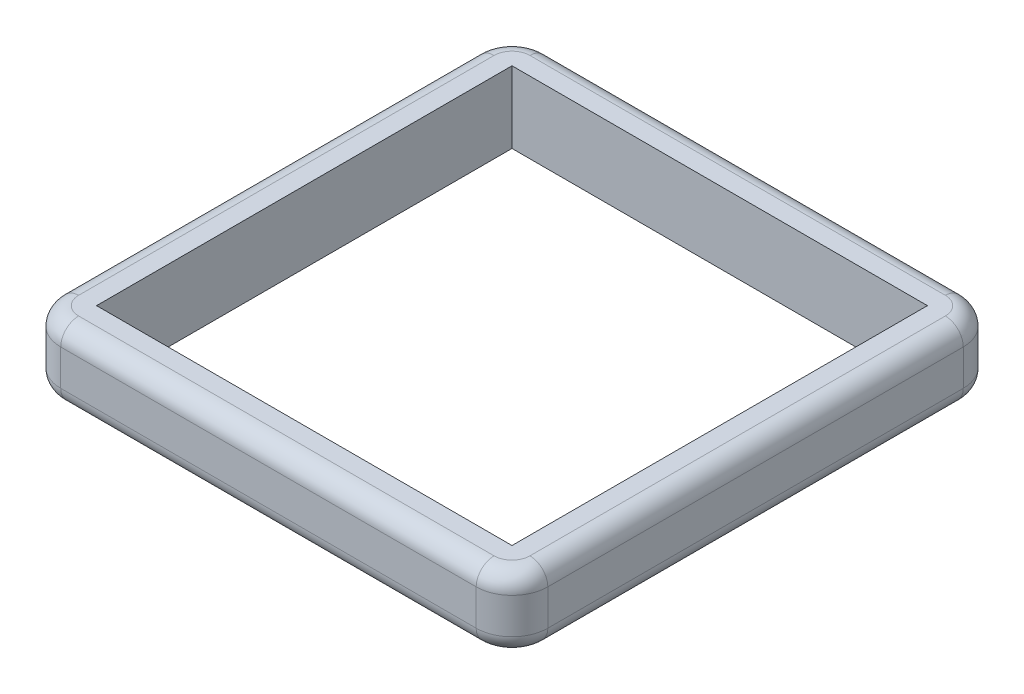
SolidWorks part; units mm, degrees
material "Polyurethane Foam Flexible"
ref_plane "Front Plane" through (0, 0, 0) normal (0, 0, 1) x (1, 0, 0)
ref_plane "Top Plane" through (0, 0, 0) normal (0, 1, 0) x (1, 0, 0)
ref_plane "Right Plane" through (0, 0, 0) normal (1, 0, 0) x (0, 0, -1)
sketch "Sketch1" plane through (0, 0, 0) normal (1, 0, 0) x (0, 0, -1)
  line L0 (-31.75, 0) -> (-31.75, -63.5)
  line L1 (31.75, 0) -> (31.75, -95.25)
  line L2 (0, -95.25) -> (31.75, -95.25)
  line L3 (31.75, 0) -> (31.75, 31.75)
  line L4 (0, 31.75) -> (31.75, 31.75)
  arc A0 (0, 31.75) -> (-31.75, 0) centre (0, 0) ccw
  arc A1 (-31.75, -63.5) -> (0, -95.25) centre (0, -63.5) ccw
  arc A2 (31.75, 0) -> (0, 31.75) centre (0, 0) ccw construction
  arc A3 (0, -31.75) -> (31.75, 0) centre (0, 0) ccw construction
  arc A4 (31.75, -63.5) -> (0, -31.75) centre (0, -63.5) ccw construction
  arc A5 (-31.75, 0) -> (0, -31.75) centre (0, 0) ccw construction
  arc A6 (0, -31.75) -> (-31.75, -63.5) centre (0, -63.5) ccw construction
  arc A7 (0, -95.25) -> (31.75, -63.5) centre (0, -63.5) ccw construction
  dimension "D1" = 63.5
  dimension "D2" = 63.5
extrude "Boss-Extrude1" add sketch "Sketch1" along normal blind 736.6 contours L0 A1 L2 L1 L3 L4 A0 region at (0, -31.75, -1.3979)
sketch "Sketch8" plane through (736.6, 0, 0) normal (1, 0, 0) x (0, 0, -1)
  line L8 (-31.75, 0) -> (-31.75, -63.5)
  line L9 (0, -95.25) -> (31.75, -95.25)
  line L10 (31.75, -95.25) -> (31.75, 31.75)
  line L11 (31.75, 31.75) -> (0, 31.75)
  line L12 (-31.75, 0) -> (-31.75, -63.5)
  line L13 (0, -95.25) -> (31.75, -95.25)
  line L14 (31.75, -95.25) -> (31.75, 31.75)
  line L15 (31.75, 31.75) -> (0, 31.75)
  arc A4 (-31.75, -63.5) -> (0, -95.25) centre (0, -63.5) ccw
  arc A5 (0, 31.75) -> (-31.75, 0) centre (0, 0) ccw
  arc A6 (-31.75, -63.5) -> (0, -95.25) centre (0, -63.5) ccw
  arc A7 (0, 31.75) -> (-31.75, 0) centre (0, 0) ccw
  dimension "D1" = 0
revolve "Revolve13" add sketch "Sketch8" angle 90 about L14
sketch "Sketch15" plane through (0, 0, -31.75) normal (-1, 0, 0) x (0, 0, 1)
  line L14 (63.5, -63.5) -> (63.5, 0)
  line L20 (31.75, 31.75) -> (0, 31.75)
  line L21 (0, 31.75) -> (0, -95.25)
  line L22 (0, -95.25) -> (31.75, -95.25)
  line L23 (63.5, -63.5) -> (63.5, 0)
  line L24 (31.75, 31.75) -> (0, 31.75)
  line L25 (0, 31.75) -> (0, -95.25)
  line L26 (0, -95.25) -> (31.75, -95.25)
  arc A8 (63.5, 0) -> (31.75, 31.75) centre (31.75, 0) ccw
  arc A9 (31.75, -95.25) -> (63.5, -63.5) centre (31.75, -63.5) ccw
  arc A10 (63.5, 0) -> (31.75, 31.75) centre (31.75, 0) ccw
  arc A11 (31.75, -95.25) -> (63.5, -63.5) centre (31.75, -63.5) ccw
  dimension "D1" = 0
revolve "Revolve12" add sketch "Sketch15" angle 90 about L25 region at (0, -31.75, -1.3979)
sketch "Sketch7" plane through (0, 0, -31.75) normal (0, 0, -1) x (-1, 0, 0)
  line L6 (-800.1, 0) -> (-800.1, -63.5)
  line L7 (-768.35, -95.25) -> (-736.6, -95.25)
  line L8 (-736.6, -95.25) -> (-736.6, 31.75)
  line L9 (-736.6, 31.75) -> (-768.35, 31.75)
  line L10 (-800.1, 0) -> (-800.1, -63.5)
  line L11 (-768.35, -95.25) -> (-736.6, -95.25)
  line L12 (-736.6, -95.25) -> (-736.6, 31.75)
  line L13 (-736.6, 31.75) -> (-768.35, 31.75)
  arc A4 (-768.35, 31.75) -> (-800.1, 0) centre (-768.35, 0) ccw
  arc A5 (-800.1, -63.5) -> (-768.35, -95.25) centre (-768.35, -63.5) ccw
  arc A6 (-768.35, 31.75) -> (-800.1, 0) centre (-768.35, 0) ccw
  arc A7 (-800.1, -63.5) -> (-768.35, -95.25) centre (-768.35, -63.5) ccw
  line M4 (-736.6, 31.75) -> (-736.6, -95.25)
  dimension "D1" = 0
extrude "Boss-Extrude3" add sketch "Sketch7" along normal blind 736.6 contours M4 | M4 region at (766.9521, -31.75, -31.75)
sketch "Sketch12" plane through (1454.15, 0, -768.35) normal (0, 0, -1) x (-1, 0, 0)
  line L13 (654.05, 0) -> (654.05, -63.5)
  line L20 (685.8, -95.25) -> (717.55, -95.25)
  line L21 (717.55, -95.25) -> (717.55, 31.75)
  line L22 (717.55, 31.75) -> (685.8, 31.75)
  line L23 (654.05, 0) -> (654.05, -63.5)
  line L24 (685.8, -95.25) -> (717.55, -95.25)
  line L25 (717.55, -95.25) -> (717.55, 31.75)
  line L26 (717.55, 31.75) -> (685.8, 31.75)
  arc A8 (654.05, -63.5) -> (685.8, -95.25) centre (685.8, -63.5) ccw
  arc A9 (685.8, 31.75) -> (654.05, 0) centre (685.8, 0) ccw
  arc A10 (654.05, -63.5) -> (685.8, -95.25) centre (685.8, -63.5) ccw
  arc A11 (685.8, 31.75) -> (654.05, 0) centre (685.8, 0) ccw
  dimension "D1" = 0
revolve "Revolve2" add sketch "Sketch12" angle 90 about L25 region at (766.9521, -31.75, -768.35)
sketch "Sketch9" plane through (0, 0, -31.75) normal (0, 0, -1) x (-1, 0, 0)
  line L0 (31.75, 31.75) -> (0, 31.75)
  line L1 (31.75, -95.25) -> (0, -95.25)
  line L2 (0, 31.75) -> (0, -95.25)
  line L3 (63.5, 0) -> (63.5, -63.5)
  line L4 (-736.6, 31.75) -> (0, 31.75) construction
  line L5 (0, -95.25) -> (0, 31.75) construction
  circle A0 centre (31.75, 0) radius 31.75
  circle A1 centre (31.75, -63.5) radius 31.75
  line M5 (0, -95.25) -> (0, 31.75)
  dimension "D1" = 63.5
  dimension "D2" = 0
  dimension "D3" = 0
extrude "Boss-Extrude4" add sketch "Sketch9" along normal blind 736.6 contours A0 L0 L2 | A0 | A1 A0 L2 | A1 L3 A0 | A1 | A1 L1 M5 region at (-7.0919, 24.6581, -31.75) region at (-31.75, 0, -31.75) region at (-56.4081, -31.75, -31.75) region at (-7.0919, -31.75, -31.75) region at (-31.75, -63.5, -31.75) region at (-7.0919, -88.1581, -31.75)
sketch "Sketch14" plane through (0, 0, -768.35) normal (0, 0, -1) x (-1, 0, 0)
  line L12 (0, 31.75) -> (0, -95.25)
  line L13 (0, -95.25) -> (31.75, -95.25)
  line L14 (63.5, -63.5) -> (63.5, 0)
  line L15 (31.75, 31.75) -> (0, 31.75)
  line L16 (0, 31.75) -> (0, -95.25)
  line L17 (0, -95.25) -> (31.75, -95.25)
  line L18 (63.5, -63.5) -> (63.5, 0)
  line L19 (31.75, 31.75) -> (0, 31.75)
  arc A4 (31.75, -95.25) -> (63.5, -63.5) centre (31.75, -63.5) ccw
  arc A5 (63.5, 0) -> (31.75, 31.75) centre (31.75, 0) ccw
  arc A6 (31.75, -95.25) -> (63.5, -63.5) centre (31.75, -63.5) ccw
  arc A7 (63.5, 0) -> (31.75, 31.75) centre (31.75, 0) ccw
  dimension "D1" = 0
revolve "Revolve10" add sketch "Sketch14" angle 90 about L16 region at (-30.3521, -31.75, -768.35)
sketch "Sketch10" plane through (0, 0, 0) normal (1, 0, 0) x (0, 0, -1)
  line L4 (800.1, 31.75) -> (768.35, 31.75)
  line L7 (768.35, 31.75) -> (768.35, -95.25)
  line L8 (768.35, -95.25) -> (800.1, -95.25)
  line L9 (831.85, -63.5) -> (831.85, 0)
  line L10 (800.1, 31.75) -> (768.35, 31.75)
  line L12 (768.35, -95.25) -> (800.1, -95.25)
  line L13 (831.85, -63.5) -> (831.85, 0)
  line L15 (768.35, 31.75) -> (768.35, -95.25)
  arc A4 (800.1, -95.25) -> (831.85, -63.5) centre (800.1, -63.5) ccw
  arc A5 (831.85, 0) -> (800.1, 31.75) centre (800.1, 0) ccw
  arc A6 (800.1, -95.25) -> (831.85, -63.5) centre (800.1, -63.5) ccw
  arc A7 (831.85, 0) -> (800.1, 31.75) centre (800.1, 0) ccw
  line M7 (768.35, -95.25) -> (768.35, 31.75)
  dimension "D1" = 0
extrude "Boss-Extrude5" add sketch "Sketch10" along normal blind 736.6 separate body contours M7 | M7 region at (0, -31.75, -798.7021)
combine bodies "Combine1" operation type add bodies to combine 105 115 108
equation "\"foamlength\"=29"
equation "\"D1@Boss-Extrude1\"=\"foamlength\""
equation "\"D1@Boss-Extrude3\"=\"foamlength\""
equation "\"D1@Boss-Extrude4\"=\"foamlength\""
equation "\"D1@Boss-Extrude5\"=\"foamlength\""
